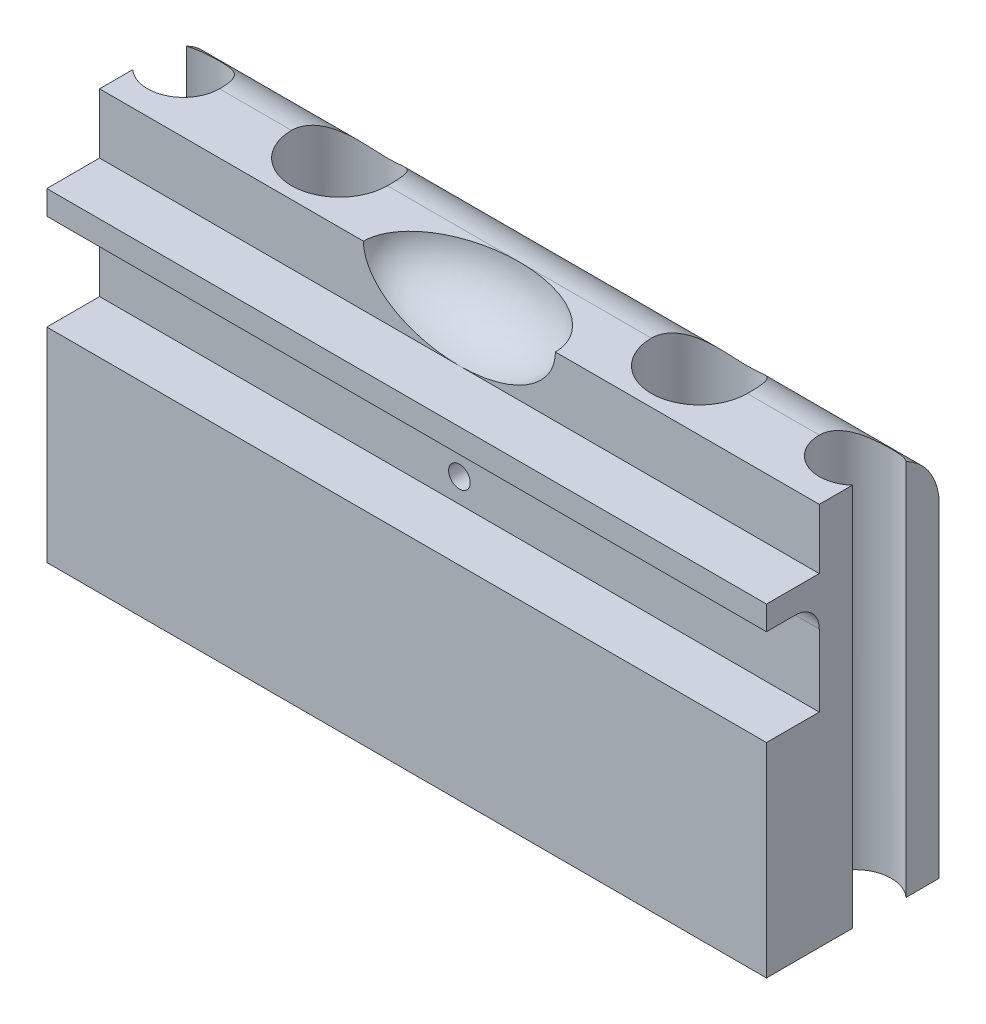
SolidWorks part; units mm, degrees
ref_plane "Front Plane" through (0, 0, 0) normal (0, 0, 1) x (1, 0, 0)
ref_plane "Top Plane" through (0, 0, 0) normal (0, 1, 0) x (1, 0, 0)
ref_plane "Right Plane" through (0, 0, 0) normal (1, 0, 0) x (0, 0, -1)
sketch "Sketch2" plane through (0, 0, 0) normal (1, 0, 0) x (0, 0, -1)
  line L1 (0, 0) -> (18.288, 0)
  line L2 (0, 0) -> (0, 40.64)
  line L3 (0, 40.64) -> (18.288, 40.64)
  line L4 (18.288, 0) -> (18.288, 40.64)
  dimension "D1" = 18.288
  dimension "D2" = 40.64
extrude "Boss-Extrude1" add sketch "Sketch2" along normal blind 76.2
sketch "Sketch3" plane through (0, 0, 0) normal (-1, 0, 0) x (0, 0, 1)
  line L0 (-18.288, 0) -> (-18.288, 40.64) construction
  line L1 (0, 40.64) -> (-5.588, 40.64)
  line L2 (0, 40.64) -> (0, 34.29)
  line L3 (0, 34.29) -> (-5.588, 34.29)
  line L4 (-5.588, 40.64) -> (-5.588, 34.29)
  line L5 (0, 40.64) -> (0, 0) construction
  line L6 (0, 31.75) -> (-5.588, 31.75)
  line L7 (0, 31.75) -> (0, 21.59)
  line L8 (0, 21.59) -> (-5.588, 21.59)
  line L9 (-5.588, 31.75) -> (-5.588, 21.59)
  dimension "D1" = 6.35
  dimension "D2" = 12.7
  dimension "D3" = 2.54
  dimension "D4" = 10.16
  dimension "D5" = 12.7
extrude "Cut-Extrude1" cut sketch "Sketch3" against normal up to next
sketch "Sketch4" plane through (0, 0, -5.588) normal (0, 0, 1) x (1, 0, 0)
  line L0 (0, 31.75) -> (0, 21.59) construction
  line L1 (76.2, 21.59) -> (0, 21.59) construction
  circle A0 centre (38.1, 24.13) radius 1.143
  dimension "D1" = 2.286
  dimension "D2" = 38.1
  dimension "D3" = 2.54
extrude "Cut-Extrude2" cut sketch "Sketch4" against normal up to next
sketch "Sketch5" plane through (0, 40.64, 0) normal (0, 1, 0) x (1, 0, 0)
  line L0 (38.1, 18.288) -> (38.1, 5.588) construction
  line L1 (76.2, 18.288) -> (0, 18.288) construction
  line L2 (76.2, 5.588) -> (0, 5.588) construction
  line L3 (76.2, 11.938) -> (0, 11.938) construction
  line L4 (76.2, 18.288) -> (76.2, 5.588) construction
  line L5 (0, 18.288) -> (0, 5.588) construction
  circle A0 centre (57.15, 11.938) radius 2.032
  circle A1 centre (19.05, 11.938) radius 2.032
  dimension "D1" = 4.064
  dimension "D2" = 4.064
  dimension "D3" = 19.05
  dimension "D4" = 19.05
extrude "Cut-Extrude3" cut sketch "Sketch5" against normal up to next
sketch "Sketch6" plane through (0, 40.64, 0) normal (0, 1, 0) x (1, 0, 0)
  circle A0 centre (19.05, 11.938) radius 5.08
  circle A1 centre (57.15, 11.938) radius 5.08
  dimension "D1" = 10.16
  dimension "D2" = 10.16
extrude "Cut-Extrude4" cut sketch "Sketch6" against normal offset from surface (15.24 mm away) 25.4 up to face at (57.15, 0, -9.906)
fillet "Fillet1" radius 6.35 1 edges at (38.1, 40.64, -18.288)
fillet "Fillet2" radius 2.54 1 edges at (38.1, 31.75, -5.588)
sketch "Sketch7" plane through (0, 0, 0) normal (0, -1, 0) x (1, 0, 0)
  line L0 (0, -11.938) -> (76.2, -11.938) construction
  line L1 (0, 0) -> (0, -18.288) construction
  line L2 (76.2, 0) -> (76.2, -18.288) construction
  line L3 (76.2, -18.288) -> (0, -18.288) construction
  circle A0 centre (2.54, -11.938) radius 3.81
  circle A1 centre (73.66, -11.938) radius 3.81
  dimension "D3" = 7.62
  dimension "D4" = 7.62
  dimension "D1" = 6.35
  dimension "D2" = 2.54
  dimension "D5" = 2.54
extrude "Cut-Extrude5" cut sketch "Sketch7" against normal through all
sketch "Sketch8" plane through (0, 0, -5.588) normal (0, 0, 1) x (1, 0, 0)
  line L0 (38.1, 40.64) -> (38.1, 34.29) construction
  line L1 (76.2, 40.64) -> (0, 40.64) construction
  line L2 (76.2, 34.29) -> (0, 34.29) construction
  line L3 (27.94, 40.64) -> (48.26, 40.64) construction
  line L4 (27.94, 40.64) -> (48.26, 40.64)
  ellipse E0 centre (38.1, 40.64) end of major axis (27.94, 40.64) minor radius 6.35 (27.94, 40.64) -> (48.26, 40.64) ccw
  dimension "D1" = 20.32
revolve "Cut-Revolve3" cut sketch "Sketch8" angle 360 about axis through (76.201, 40.64, -5.588) along (-1, 0, 0) reverse direction yes
